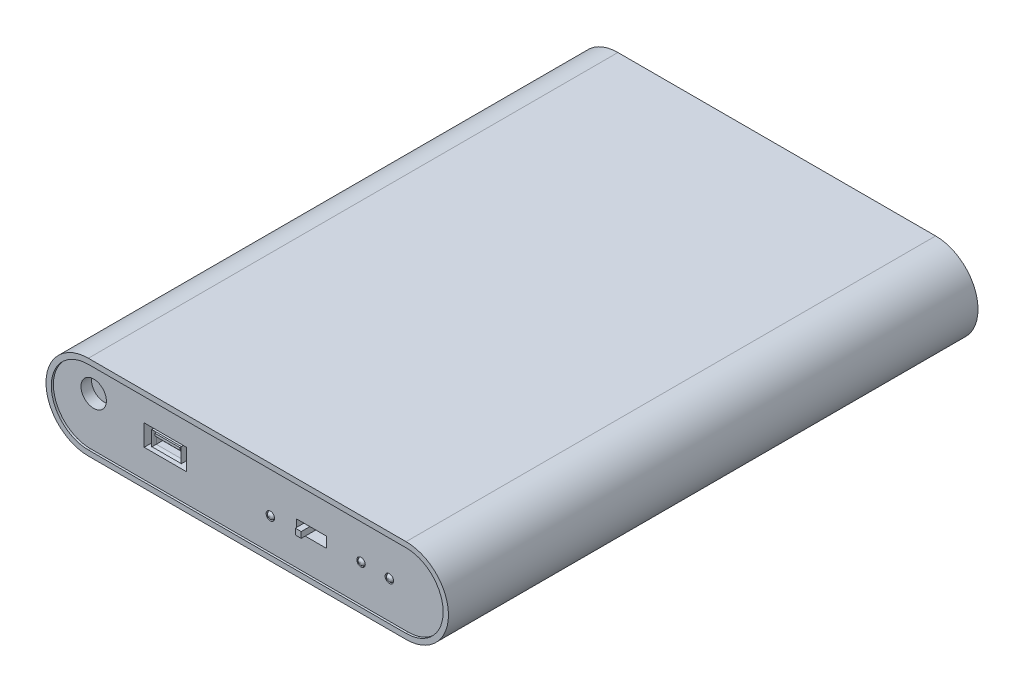
SolidWorks part; units mm, degrees
ref_plane "前视基准面" through (0, 0, 0) normal (0, 0, 1) x (1, 0, 0)
ref_plane "上视基准面" through (0, 0, 0) normal (0, 1, 0) x (1, 0, 0)
ref_plane "右视基准面" through (0, 0, 0) normal (1, 0, 0) x (0, 0, -1)
sketch "草图1" plane through (0, 0, 0) normal (0, 0, 1) x (1, 0, 0)
  line L1 (-75, 20) -> (75, 20)
  line L3 (-75, -20) -> (75, -20)
  arc A0 (-75, 20) -> (-75, -20) centre (-75, 0) ccw
  arc A1 (75, -20) -> (75, 20) centre (75, 0) ccw
  point P0 (0, 0)
  dimension "D1" = 150
  dimension "D8" = 20
  dimension "D9" = 20
extrude "凸台-拉伸1" add sketch "草图1" along normal blind 250
sketch "草图2" plane through (0, 0, 0) normal (0, 0, -1) x (-1, 0, 0)
  circle A0 centre (24, -8) radius 4
  circle A1 centre (48, -8) radius 4
  circle A3 centre (0, -8) radius 4
  circle A4 centre (-24, -8) radius 4
  circle A5 centre (-48, -8) radius 4
  circle A6 centre (-48, 8) radius 4
  circle A7 centre (-24, 8) radius 4
  circle A8 centre (0, 8) radius 4
  circle A9 centre (24, 8) radius 4
  circle A10 centre (48, 8) radius 4
  point P23 (1.3438, 2.0055)
  point P25 (-36, -6.324)
  point P26 (-60, -0.2087)
  point P27 (-60, -4.551)
  point P28 (-12, -4.551)
  point P29 (12, -4.551)
  point P30 (36, -4.551)
  point P31 (60, -4.551)
  point P34 (-11.4106, 5.4815)
  dimension "D7" = 8
  dimension "D2" = 0
  dimension "D3" = 24
  dimension "D4" = 24
  dimension "D5" = 24
  dimension "D6" = 24
  dimension "D8" = 24
  dimension "D9" = 24
  dimension "D10" = 0
  dimension "D11" = 24
  dimension "D12" = 24
  dimension "D13" = 8
  dimension "D15" = 8
  dimension "D16" = 8
extrude "切除-拉伸1" cut sketch "草图2" against normal blind 5
sketch "草图3" plane through (0, 0, 0) normal (0, 0, -1) x (-1, 0, 0)
  circle A0 centre (-48, -8) radius 6
  circle A1 centre (-24, -8) radius 6
  circle A3 centre (24, -8) radius 6
  circle A4 centre (48, -8) radius 6
  circle A6 centre (-48, -8) radius 5.8
  circle A7 centre (-24, -8) radius 5.8
  circle A8 centre (0, -8) radius 6
  circle A9 centre (24, -8) radius 5.8
  circle A10 centre (0, -8) radius 5.8
  circle A11 centre (48, -8) radius 5.8
  circle A13 centre (-48, 8) radius 6
  circle A14 centre (-24, 8) radius 6
  circle A15 centre (0, 8) radius 6
  circle A16 centre (24, 8) radius 6
  circle A17 centre (48, 8) radius 6
  circle A20 centre (48, 8) radius 5.8
  circle A21 centre (24, 8) radius 5.8
  circle A22 centre (0, 8) radius 5.8
  circle A23 centre (-24, 8) radius 5.8
  circle A24 centre (-48, 8) radius 5.8
extrude "切除-拉伸2" cut sketch "草图3" against normal blind 5
fillet "圆角1" radius 0.5 20 edges at (44, -8, 0) (42.2, -8, 0) (-53.8, -8, 0) (-52, -8, 0) (-29.8, -8, 0) (-28, -8, 0) (-4, -8, 0) (-5.8, -8, 0) (20, -8, 0) (18.2, -8, 0) (-52, 8, 0) (-28, 8, 0) (-4, 8, 0) (44, 8, 0) (20, 8, 0) (-53.8, 8, 0) (-29.8, 8, 0) (-5.8, 8, 0) (18.2, 8, 0) (42.2, 8, 0)
sketch "草图4" plane through (0, 0, 0) normal (0, 0, -1) x (-1, 0, 0)
  line L5 (-75, -17.5) -> (75, -17.5)
  line L7 (-75, 17.5) -> (75, 17.5)
  circle A2 centre (-48, -8) radius 6
  circle A3 centre (-24, -8) radius 6
  circle A4 centre (0, -8) radius 6
  circle A6 centre (48, -8) radius 6
  circle A8 centre (24, -8) radius 6
  arc A11 (-75, 17.5) -> (-75, -17.5) centre (-75, 0) ccw
  arc A12 (75, -17.5) -> (75, 17.5) centre (75, 0) ccw
  circle A13 centre (-48, 8) radius 6
  circle A14 centre (-24, 8) radius 6
  circle A15 centre (0, 8) radius 6
  circle A16 centre (24, 8) radius 6
  circle A17 centre (48, 8) radius 6
  point P0 (0, 0)
  point P1 (0, 0)
extrude "切除-拉伸3" cut sketch "草图4" against normal blind 1
sketch "草图5" plane through (0, 0, 250) normal (0, 0, 1) x (1, 0, 0)
  line L1 (-75, -17.5) -> (75, -17.5)
  line L3 (-75, 17.5) -> (75, 17.5)
  arc A0 (-75, 17.5) -> (-75, -17.5) centre (-75, 0) ccw
  arc A1 (75, -17.5) -> (75, 17.5) centre (75, 0) ccw
  point P0 (0, 0)
extrude "切除-拉伸4" cut sketch "草图5" against normal blind 1
sketch "草图6" plane through (0, 0, 249) normal (0, 0, 1) x (1, 0, 0)
  line L1 (-49.6585, 5.7616) -> (-29.6585, 5.7616)
  line L2 (-49.6585, 5.7616) -> (-49.6585, -4.2384)
  line L3 (-49.6585, -4.2384) -> (-29.6585, -4.2384)
  line L4 (-29.6585, 5.7616) -> (-29.6585, -4.2384)
  line L5 (-49.6585, 5.7616) -> (-29.6585, -4.2384) construction
  line L6 (-49.6585, -4.2384) -> (-29.6585, 5.7616) construction
  line L7 (22.3263, 2.464) -> (36.3263, 2.464)
  line L8 (22.3263, 2.464) -> (22.3263, -2.536)
  line L9 (22.3263, -2.536) -> (36.3263, -2.536)
  line L10 (36.3263, 2.464) -> (36.3263, -2.536)
  line L11 (22.3263, 2.464) -> (36.3263, -2.536) construction
  line L12 (22.3263, -2.536) -> (36.3263, 2.464) construction
  circle A0 centre (-73.4913, 5.7616) radius 6
  circle A1 centre (52.7254, -0.036) radius 2
  circle A2 centre (66.1009, -0.036) radius 2
  circle A3 centre (9.9236, -2.536) radius 2
  point P0 (-39.6585, 0.7616)
  point P7 (29.3263, -0.036)
extrude "切除-拉伸5" cut sketch "草图6" against normal blind 5
sketch "草图7" plane through (0, 0, 244) normal (0, 0, 1) x (1, 0, 0)
  circle A0 centre (9.9236, -2.536) radius 1.8
  circle A1 centre (52.7254, -0.036) radius 1.8
  circle A2 centre (66.1009, -0.036) radius 1.8
extrude "凸台-拉伸2" add sketch "草图7" along normal blind 5.5
fillet "圆角2" radius 1.5 3 edges at (67.9009, -0.036, 249.5) (54.5254, -0.036, 249.5) (11.7236, -2.536, 249.5)
sketch "草图8" plane through (0, 0, 244) normal (0, 0, 1) x (1, 0, 0)
  line L1 (24.6961, 1.3845) -> (27.4961, 1.3845)
  line L2 (24.6961, 1.3845) -> (24.6961, -1.4155)
  line L3 (24.6961, -1.4155) -> (27.4961, -1.4155)
  line L4 (27.4961, 1.3845) -> (27.4961, -1.4155)
  line L5 (24.6961, 1.3845) -> (27.4961, -1.4155) construction
  line L6 (24.6961, -1.4155) -> (27.4961, 1.3845) construction
  point P0 (26.0961, -0.0155)
extrude "凸台-拉伸3" add sketch "草图8" along normal blind 8
sketch "草图9" plane through (0, 0, 244) normal (0, 0, 1) x (1, 0, 0)
  line L1 (27.4961, 1.3845) -> (32.4961, 1.3845)
  line L2 (27.4961, 1.3845) -> (27.4961, -1.4155)
  line L3 (27.4961, -1.4155) -> (32.4961, -1.4155)
  line L4 (32.4961, 1.3845) -> (32.4961, -1.4155)
extrude "凸台-拉伸4" add sketch "草图9" along normal blind 1
sketch "草图10" plane through (0, 0, 244) normal (0, 0, 1) x (1, 0, 0)
  line L1 (-46.6585, 4.2616) -> (-32.6585, 4.2616)
  line L2 (-46.6585, 4.2616) -> (-46.6585, -2.7384)
  line L3 (-46.6585, -2.7384) -> (-32.6585, -2.7384)
  line L4 (-32.6585, 4.2616) -> (-32.6585, -2.7384)
  line L5 (-45.9085, 3.6616) -> (-33.4085, 3.6616)
  line L6 (-45.9085, 3.6616) -> (-45.9085, -2.1384)
  line L7 (-45.9085, -2.1384) -> (-33.4085, -2.1384)
  line L8 (-33.4085, 3.6616) -> (-33.4085, -2.1384)
  line L9 (-45.9085, 3.6616) -> (-33.4085, -2.1384) construction
  line L10 (-45.9085, -2.1384) -> (-33.4085, 3.6616) construction
  point P0 (-39.6585, 0.7616)
  point P6 (-39.6585, 0.7616)
extrude "凸台-拉伸5" add sketch "草图10" along normal blind 5
fillet "圆角3" radius 2 4 edges at (-33.4085, 0.7616, 249) (-39.6585, -2.1384, 249) (-45.9085, 0.7616, 249) (-39.6585, 3.6616, 249)
sketch "草图11" plane through (0, 0, 244) normal (0, 0, 1) x (1, 0, 0)
  line L1 (-45.6585, 3.0566) -> (-33.6585, 3.0566)
  line L2 (-45.6585, 3.0566) -> (-45.6585, 1.9256)
  line L3 (-45.6585, 1.9256) -> (-33.6585, 1.9256)
  line L4 (-33.6585, 3.0566) -> (-33.6585, 1.9256)
  line L5 (-45.6585, 3.0566) -> (-33.6585, 1.9256) construction
  line L6 (-45.6585, 1.9256) -> (-33.6585, 3.0566) construction
  point P0 (-39.6585, 2.4911)
extrude "凸台-拉伸6" add sketch "草图11" along normal blind 4
